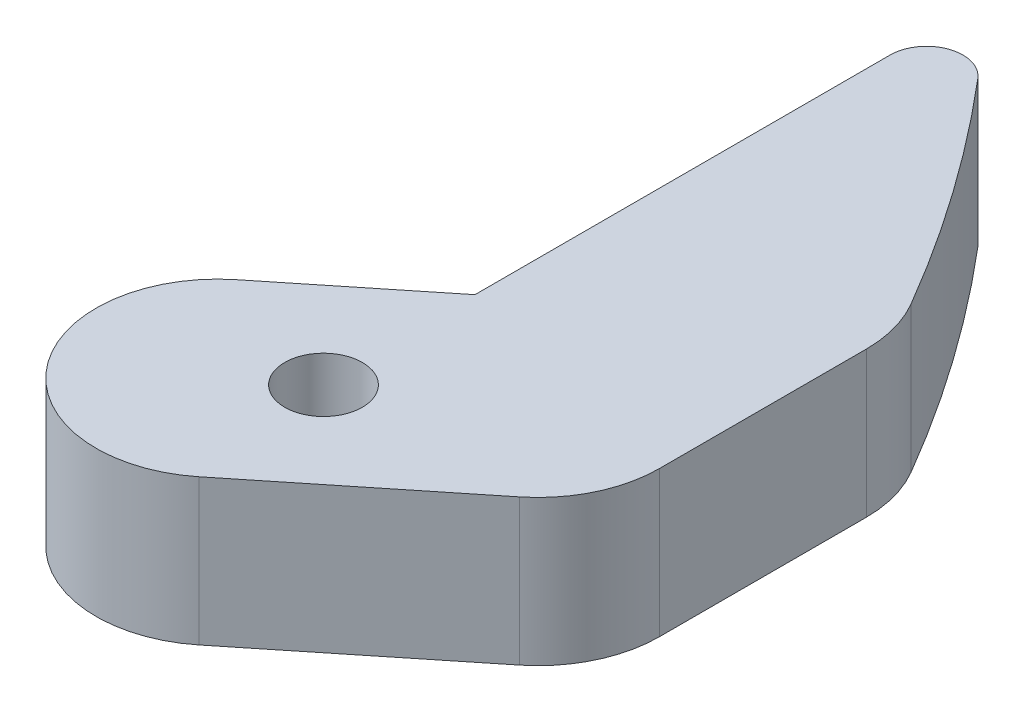
SolidWorks part; units mm, degrees
ref_plane "Plano frontal" through (0, 0, 0) normal (0, 0, 1) x (1, 0, 0)
ref_plane "Plano superior" through (0, 0, 0) normal (0, 1, 0) x (1, 0, 0)
ref_plane "Plano direito" through (0, 0, 0) normal (1, 0, 0) x (0, 0, -1)
ref_plane "Plano1" through (0, -12, 0) normal (0, -1, 0) x (1, 0, 0)
sketch "Esboço1" plane through (0, -12, 0) normal (0, -1, 0) x (1, 0, 0)
  line L0 (-5.5544, -1.9504) -> (-0.0984, -6.3359)
  line L1 (-0.0984, -6.3359) -> (-0.0984, -23.4342)
  line L2 (9.9016, -12.4543) -> (9.9016, -3.9398)
  line L3 (8.034, -0.0427) -> (0.7105, 5.8439)
  line L4 (0, 0) -> (-28.7366, 23.0979) construction
  line L5 (-3.1324, -3.8971) -> (3.1324, 3.8971) construction
  arc A0 (0.7105, 5.8439) -> (-5.5544, -1.9504) centre (-2.422, 1.9467) ccw
  arc A1 (-0.0984, -23.4342) -> (2.5451, -24.405) centre (1.4016, -23.4342) ccw
  arc A2 (2.5451, -24.405) -> (9.2207, -14.9732) centre (-47.5984, 18.1641) ccw
  arc A3 (9.2207, -14.9732) -> (9.9016, -12.4543) centre (4.9016, -12.4543) ccw
  arc A4 (9.9016, -3.9398) -> (8.034, -0.0427) centre (4.9016, -3.9398) ccw
  circle A5 centre (0, 0) radius 1.6
  point P19 (0, 0)
  point P20 (0, 0)
  dimension "D1" = 3.2
  dimension "D3" = 1.5
  dimension "D7" = 23.4342
  dimension "D8" = 65.7761
  dimension "D2" = 10
  dimension "D4" = 10
  dimension "D5" = 6.2887
  dimension "D6" = 3.1073
  dimension "D9" = 6.3359
  dimension "D10" = 12.4543
extrude "Ressalto-extrusão1" add sketch "Esboço1" against normal blind 6
